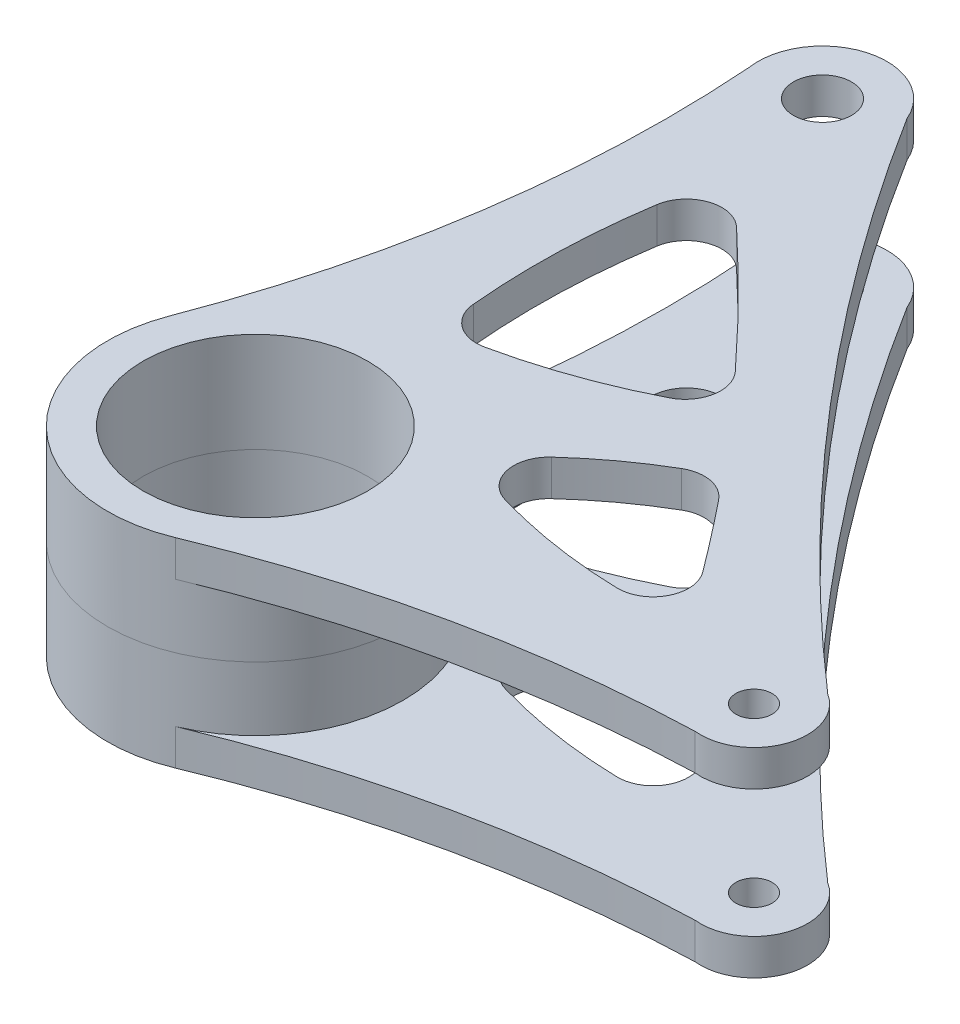
SolidWorks part; units mm, degrees
ref_plane "Front Plane" through (0, 0, 0) normal (0, 0, 1) x (1, 0, 0)
ref_plane "Top Plane" through (0, 0, 0) normal (0, 1, 0) x (1, 0, 0)
ref_plane "Right Plane" through (0, 0, 0) normal (1, 0, 0) x (0, 0, -1)
sketch "Sketch1" plane through (0, 0, 0) normal (0, 1, 0) x (1, 0, 0)
  line L0 (0, 80) -> (0, 0) construction
  line L1 (-9.0011, 81.338) -> (-20.6356, 3.0674)
  line L2 (6.9286, 85.8995) -> (74.8576, 6.1217)
  line L3 (4.3808, -20.3972) -> (70.6945, -6.1546)
  circle A0 centre (0, 0) radius 15.8623
  circle A1 centre (0, 80) radius 4.1
  circle A2 centre (69.1091, 1.2271) radius 2.55
  circle A3 centre (0, 80) radius 9.1
  circle A4 centre (0, 0) radius 20.8623
  circle A5 centre (69.1091, 1.2271) radius 7.55
  dimension "D1" = 8.2
  dimension "1" = 31.7246
  dimension "D3" = 5.1
  dimension "D5" = 69.12
  dimension "D4" = 80
  dimension "D6" = 5
extrude "Boss-Extrude1" add sketch "Sketch1" along normal blind 5.08 contours A1 A3 | A3 L0 A4 L3 A5 L2 | A4 A0 | L0 A3 L1 A4 | A5 A2 region at (-6.6966, 0, -74.2253) region at (29.5673, 0, -26.3622) region at (-7.9105, 0, -42.4424) region at (14.3346, 0, -14.3346) region at (75.994, 0, -3.7611)
sketch "Sketch3" plane through (0, 5.08, 0) normal (0, 1, 0) x (1, 0, 0)
  line L23 (6.9286, 85.8995) -> (74.8576, 6.1217) construction
  line L24 (6.9286, 85.8995) -> (74.8576, 6.1217)
  circle A29 centre (0, 80) radius 9.1
  circle A30 centre (0, 0) radius 20.8623
  circle A31 centre (69.1091, 1.2271) radius 7.55
  arc A32 (1.124, 24.8547) -> (31.4163, 35.8255) centre (-9.9767, 102.8121) ccw
  arc A33 (-9.1, 80) -> (-19.488, 7.4468) centre (-174.4184, 66.6496) cw
  arc A34 (7.9798, -19.2758) -> (68.3218, -6.2818) centre (73.7743, -178.2079) cw
  arc A35 (70.6945, -6.1546) -> (74.8576, 6.1217) centre (69.1091, 1.2271) ccw construction
  arc A36 (-20.6356, 3.0674) -> (4.3808, -20.3972) centre (0, 0) ccw construction
  arc A37 (6.9286, 85.8995) -> (-9.0011, 81.338) centre (0, 80) ccw construction
  arc A38 (3.0418, 64.268) -> (1.799, 20.7846) centre (102.9531, 39.6531) ccw
  arc A39 (3.0418, 64.268) -> (54.8896, 6.1217) centre (-221.7632, -188.3747) cw
  arc A40 (16.9411, 12.1752) -> (66.9551, 8.4633) centre (47.0346, 78.8536) ccw
  arc A41 (39.0442, 26.9044) -> (19.0809, 11.2502) centre (66.1753, -28.2515) ccw
  arc A42 (6.9286, 85.8995) -> (74.8576, 6.1217) centre (295.1167, 262.4762) ccw
  point P32 (16.9411, 12.1752)
  line M15 (-9.0011, 81.338) -> (-20.6356, 3.0674)
  line M17 (4.3808, -20.3972) -> (70.6945, -6.1546)
  line M19 (74.8576, 6.1217) -> (6.9286, 85.8995)
extrude "Cut-Extrude1" cut sketch "Sketch3" against normal through all contours A33 A29 A30 M15 | A39 A29 A38 A32 | A39 A41 A40 | A34 A30 A31 M17 | A29 A42 A31 M19 region at (39.6539, 5.08, -44.9415) region at (-12.9781, 5.08, -42.6179) region at (38.0045, 5.08, 11.8867) region at (37.1781, 5.08, -14.1079) region at (11.4604, 5.08, -41.4426)
fillet "Fillet1" radius 5 6 edges at (54.8896, 2.54, -6.1217) (19.0809, 2.54, -11.2502) (39.0442, 2.54, -26.9044) (31.4163, 2.54, -35.8255) (1.124, 2.54, -24.8547) (3.0418, 2.54, -64.268)
sketch "Sketch2" plane through (0, 5.08, 0) normal (0, 1, 0) x (1, 0, 0)
  arc A1 (-19.488, 7.4468) -> (7.9798, -19.2758) centre (0, 0) ccw construction
  circle A7 centre (0, 0) radius 15.25
  circle A8 centre (0, 0) radius 20.8623
  arc A9 (68.3218, -6.2818) -> (7.9798, -19.2758) centre (73.7743, -178.2079) ccw construction
  arc A10 (-19.488, 7.4468) -> (-8.994, 78.615) centre (-174.4184, 66.6496) ccw construction
  arc A11 (68.3218, -6.2818) -> (7.9798, -19.2758) centre (73.7743, -178.2079) ccw
  arc A12 (-19.488, 7.4468) -> (-8.994, 78.615) centre (-174.4184, 66.6496) ccw
  arc M7 (-19.488, 7.4468) -> (7.9798, -19.2758) centre (0, 0) ccw
  circle M14 centre (0, 0) radius 15.8623
extrude "Boss-Extrude2" add sketch "Sketch2" along normal blind 9 contours A8 M7 M14 region at (16.8546, 5.08, 11.2643)
mirror "Mirror1" about plane through (0, 14.08, 0) normal (0, 1, 0) of bodies 102
ref_plane "Plane1" through (0, 14.08, 0) normal (0, -1, 0) x (-1, 0, 0)
ref_axis "Axis1" through (69.1091, 5.08, -1.2271) along (0, -1, 0)
ref_point "Pushrod Pt"
sketch "Sketch4" plane through (0, 14.08, 0) normal (0, -1, 0) x (-1, 0, 0)
  line L0 (0, 80) -> (0, 0)
  line L1 (0, 0) -> (-69.1091, 1.2271)
  line L2 (-69.1091, 1.2271) -> (0, 80)
sketch "Sketch5" plane through (0, 28.16, 0) normal (0, 1, 0) x (1, 0, 0)
  arc A0 (8.3738, 83.5622) -> (-8.994, 78.615) centre (0, 80) ccw construction
  arc A1 (-19.488, 7.4468) -> (7.9798, -19.2758) centre (0, 0) ccw construction
  point P0 (0, 89.1)
  point P1 (0, -20.8623)
  point P5 (76.7063, 1.2271)
  point P9 (-20.8623, 0)
  dimension "D1" = 109.9623
  dimension "D2" = 97.5686
